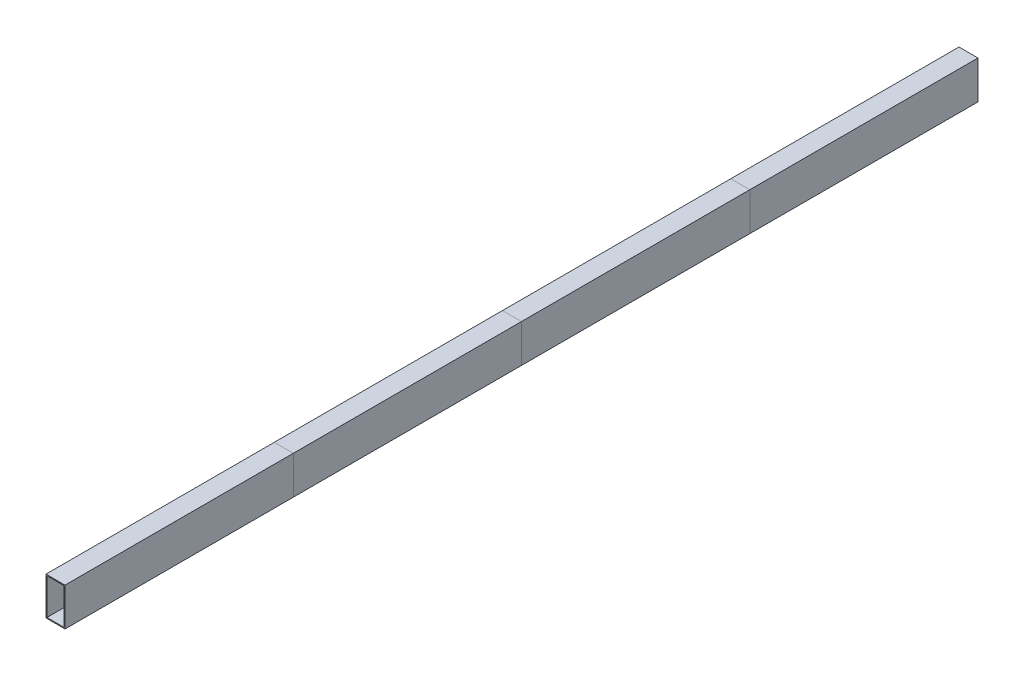
SolidWorks part; units mm, degrees
ref_plane "Спереди" through (0, 0, 0) normal (0, 0, 1) x (1, 0, 0)
ref_plane "Сверху" through (0, 0, 0) normal (0, 1, 0) x (1, 0, 0)
ref_plane "Справа" through (0, 0, 0) normal (1, 0, 0) x (0, 0, -1)
sketch "Эскиз1" plane through (0, 0, 0) normal (0, 0, 1) x (1, 0, 0)
  line L1 (-50, -100) -> (50, -100)
  line L2 (-50, -100) -> (-50, 100)
  line L3 (-50, 100) -> (50, 100)
  line L4 (50, -100) -> (50, 100)
  line L5 (-50, -100) -> (50, 100) construction
  line L6 (-50, 100) -> (50, -100) construction
  line L7 (-45, -95) -> (45, -95)
  line L8 (-45, -95) -> (-45, 95)
  line L9 (-45, 95) -> (45, 95)
  line L10 (45, -95) -> (45, 95)
  line L11 (-45, -95) -> (45, 95) construction
  line L12 (-45, 95) -> (45, -95) construction
  point P0 (0, 0)
  point P7 (0, 0)
  dimension "D1" = 100
  dimension "D2" = 200
  dimension "D3" = 90
  dimension "D4" = 190
extrude "Бобышка-Вытянуть1" add sketch "Эскиз1" along normal blind 1200
extrude "Бобышка-Вытянуть2" add sketch "Эскиз1<2>" along normal blind 1200 from surface separate body starting at face at (0, 0, 1200)
sketch "Эскиз1<2>" plane through (0, 0, 0) normal (0, 0, 1) x (1, 0, 0) same geometry as "Эскиз1"
extrude "Бобышка-Вытянуть3" add sketch "Эскиз1<3>" along normal blind 1200 from surface separate body starting at face at (0, 0, 2400)
sketch "Эскиз1<3>" plane through (0, 0, 0) normal (0, 0, 1) x (1, 0, 0) same geometry as "Эскиз1"
extrude "Бобышка-Вытянуть4" add sketch "Эскиз1<4>" along normal blind 1200 from surface separate body starting at face at (0, 0, 3600)
sketch "Эскиз1<4>" plane through (0, 0, 0) normal (0, 0, 1) x (1, 0, 0) same geometry as "Эскиз1"
ref_point "Точка1"
ref_point "Точка2"
